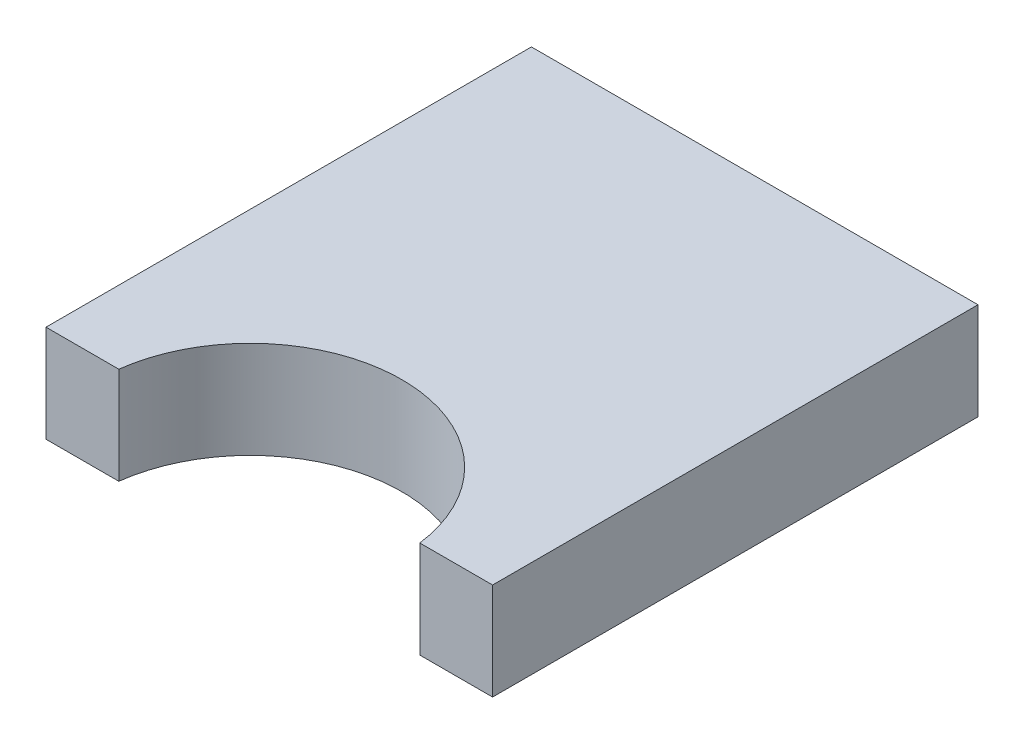
SolidWorks part; units mm, degrees
material "PLA"
ref_plane "Front" through (0, 0, 0) normal (0, 0, 1) x (1, 0, 0)
ref_plane "Top" through (0, 0, 0) normal (0, 1, 0) x (1, 0, 0)
ref_plane "Right" through (0, 0, 0) normal (1, 0, 0) x (0, 0, -1)
sketch "Sketch2" plane through (0, 0, 0) normal (0, 1, 0) x (1, 0, 0)
  line L0 (-14.986, -38.1) -> (-7.366, -38.1)
  line L1 (-14.986, 12.7) -> (31.75, 12.7)
  line L2 (-14.986, 12.7) -> (-14.986, -38.1)
  line L4 (31.75, 12.7) -> (31.75, -38.1)
  line L5 (24.13, -38.1) -> (31.75, -38.1)
  arc A3 (24.13, -38.1) -> (-7.366, -38.1) centre (8.382, -40.104) ccw
  point P0 (0, 0)
  dimension "D5" = 31.75
  dimension "D2" = 50.8
  dimension "D1" = 46.736
  dimension "D3" = 7.62
  dimension "D4" = 7.62
extrude "Boss-Extrude1" add sketch "Sketch2" against normal blind 10.16
sketch "Sketch6" plane through (0, 0, -12.7) normal (0, 0, -1) x (-1, 0, 0)
  line L0 (0, 0) -> (14.986, 0)
  line L1 (14.986, 0) -> (-31.75, 0)
  line L2 (-31.75, 0) -> (-8.382, 0)
  line L3 (-8.382, 0) -> (-8.382, -10.16)
  line L6 (-8.382, -5.08) -> (14.986, -5.08)
  line L7 (14.986, -10.16) -> (14.986, 0) construction
  line L8 (14.986, -5.08) -> (-31.75, -5.08)
  line L9 (-31.75, -10.16) -> (-31.75, 0) construction
  line L10 (-27.94, -5.08) -> (-8.382, -5.08)
  line L11 (-8.382, -5.08) -> (11.176, -5.08)
  circle A0 centre (-27.94, -5.08) radius 1.0033
  circle A1 centre (11.176, -5.08) radius 1.0033
  dimension "D2" = 2.0066
  dimension "D5" = 2.0066
  dimension "D1" = 23.368
  dimension "D3" = 19.558
  dimension "D4" = 19.558
extrude "Cut-Extrude1" cut sketch "Sketch6" against normal blind 4.064 contours L10 A0 L8 | L8 A0 L10 | L8 A1 L11 | L11 A1 L8 region at (-11.176, -4.6542, -12.7) region at (-11.176, -5.5058, -12.7) region at (27.94, -5.5058, -12.7) region at (27.94, -4.6542, -12.7)
